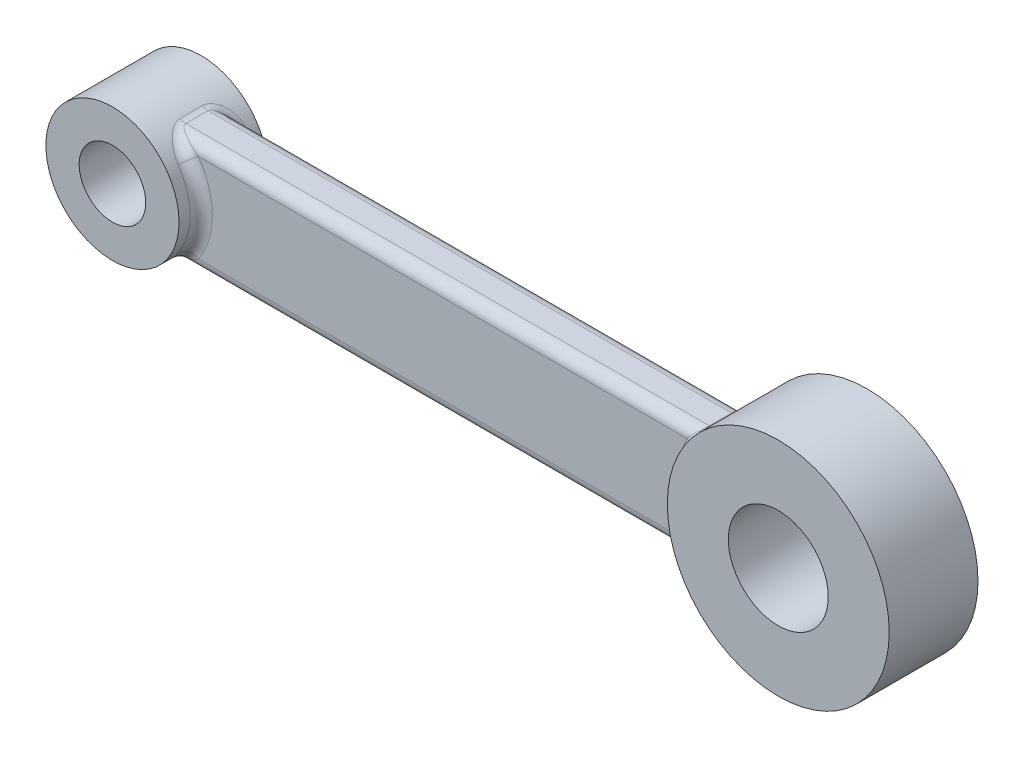
SolidWorks part; units mm, degrees
ref_plane "Front Plane" through (0, 0, 0) normal (0, 0, 1) x (1, 0, 0)
ref_plane "Top Plane" through (0, 0, 0) normal (0, 1, 0) x (1, 0, 0)
ref_plane "Right Plane" through (0, 0, 0) normal (1, 0, 0) x (0, 0, -1)
sketch "Sketch1" plane through (0, 0, 0) normal (0, 0, 1) x (1, 0, 0)
  line L1 (-15, 2.5) -> (15, 2.5)
  line L2 (-15, 2.5) -> (-15, -2.5)
  line L3 (-15, -2.5) -> (15, -2.5)
  line L4 (15, 2.5) -> (15, -2.5)
  line L5 (-15, 2.5) -> (15, -2.5) construction
  line L6 (-15, -2.5) -> (15, 2.5) construction
  point P0 (0, 0)
  dimension "D1" = 30
  dimension "D2" = 5
extrude "Boss-Extrude2" add sketch "Sketch1" along normal mid plane 2
sketch "Sketch4" plane through (0, 0, 0) normal (0, 0, 1) x (1, 0, 0)
  line L0 (0, 5.9144) -> (0, -5.2238) construction
  line L1 (-18.2241, 0) -> (16.6964, 0) construction
  line L2 (-15, 2.5) -> (-15, -2.5) construction
  line L3 (15, -2.5) -> (15, 2.5) construction
  circle A0 centre (-15, 0) radius 3
  circle A1 centre (15, 0) radius 5
  dimension "D1" = 10
  dimension "D2" = 6
extrude "Boss-Extrude3" add sketch "Sketch4" along normal mid plane 4
sketch "Sketch5" plane through (0, 0, 2) normal (0, 0, 1) x (1, 0, 0)
  line L0 (0, 6.0618) -> (0, -8.5424) construction
  line L1 (-21.5041, 0) -> (21.7974, 0) construction
  circle A0 centre (15, 0) radius 2.25
  circle A2 centre (-15, 0) radius 1.5
  dimension "D1" = 3
  dimension "D2" = 4.5
extrude "Cut-Extrude1" cut sketch "Sketch5" against normal through all
fillet "Fillet1" radius 0.5 4 edges at (-1.3359, -2.5, 1) (-1.3359, -2.5, -1) (-1.3359, 2.5, -1) (-1.3359, 2.5, 1)
fillet "Fillet2" radius 0.5 8 edges at (-13.1981, 2.3986, 0.8019) (-13.3417, 2.5, 0) (-13.2762, 2.4553, -0.7066) (-12, 0, -1) (-13.1981, -2.3986, -0.8019) (-13.3417, -2.5, 0) (-13.2762, -2.4553, 0.7066) (-12, 0, 1)
fillet "Fillet3" radius 0.5 8 edges at (10.6204, -2.4123, -0.7829) (10.6699, -2.5, 0) (10.5801, -2.3376, 0.8688) (10, 0, 1) (10.6204, 2.4123, 0.7829) (10.6699, 2.5, 0) (10.5801, 2.3376, -0.8688) (10, 0, -1)
